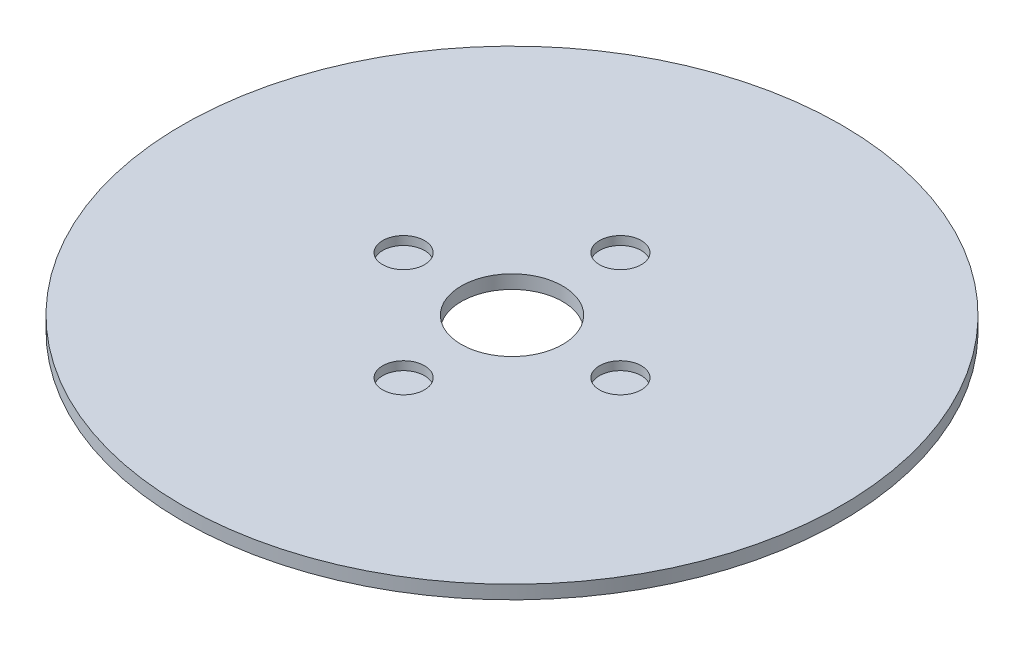
SolidWorks part; units mm, degrees
ref_plane "Front Plane" through (0, 0, 0) normal (0, 0, 1) x (1, 0, 0)
ref_plane "Top Plane" through (0, 0, 0) normal (0, 1, 0) x (1, 0, 0)
ref_plane "Right Plane" through (0, 0, 0) normal (1, 0, 0) x (0, 0, -1)
sketch "Sketch1" plane through (0, 0, 0) normal (0, 1, 0) x (1, 0, 0)
  circle A0 centre (0, 0) radius 97.5
  dimension "FLANGE_OD" = 195
extrude "Boss-Extrude1" add sketch "Sketch1" along normal blind 4
sketch "Sketch2" plane through (0, 0, 0) normal (0, 1, 0) x (1, 0, 0)
  circle A0 centre (0, 0) radius 15
  dimension "BORE_D" = 30
extrude "Cut-Extrude1" cut sketch "Sketch2" along normal through all
sketch "Sketch3" plane through (0, 4, 0) normal (0, 1, 0) x (1, 0, 0)
  circle A0 centre (0, 0) radius 32.0719 construction
  circle A1 centre (-32.0719, 0) radius 6.1905
  dimension "BOLT_D" = 12.381
  dimension "BOLT_PCD" = 64.1438
extrude "Cut-Extrude2" cut sketch "Sketch3" against normal blind 2.5531
pattern_circular "CirPattern1" count 4 over 360 about axis through (0, 0, 0) along (0, 1, 0) of "Cut-Extrude2"
